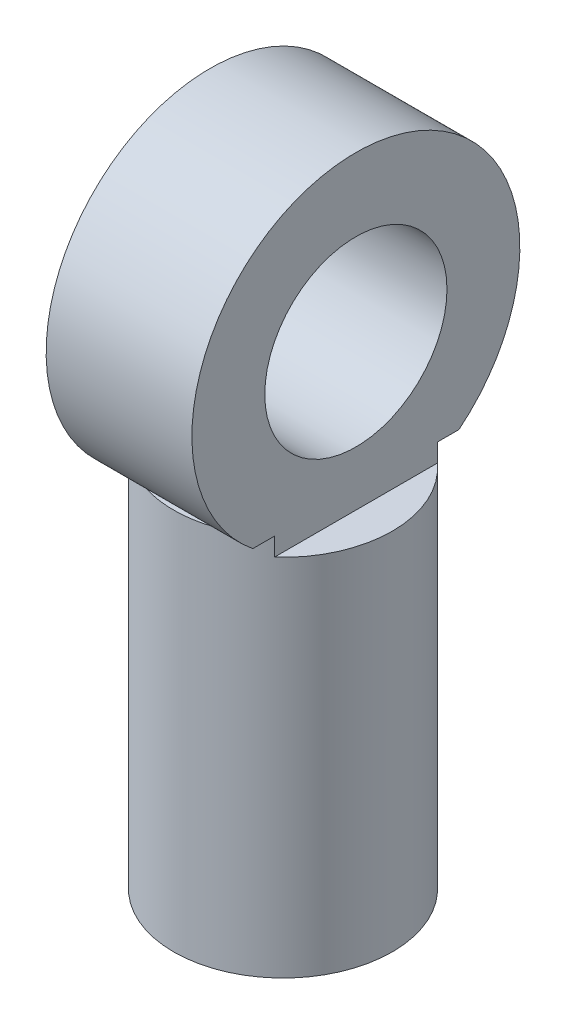
SolidWorks part; units mm, degrees
ref_plane "Front Plane" through (0, 0, 0) normal (0, 0, 1) x (1, 0, 0)
ref_plane "Top Plane" through (0, 0, 0) normal (0, 1, 0) x (1, 0, 0)
ref_plane "Right Plane" through (0, 0, 0) normal (1, 0, 0) x (0, 0, -1)
sketch "Sketch1" plane through (0, 0, 0) normal (0, 1, 0) x (1, 0, 0)
  circle A0 centre (0, 0) radius 3
  dimension "D1" = 6
extrude "crank_body" add sketch "Sketch1" along normal blind 10
sketch "Sketch2" plane through (0, 0, 0) normal (0, -1, 0) x (1, 0, 0)
  circle A0 centre (0, 0) radius 1.65
  dimension "D1" = 3.3
extrude "dowel_shaft" cut sketch "Sketch2" against normal blind 9
sketch "Sketch3" plane through (0, 0, 0) normal (1, 0, 0) x (0, 0, -1)
  line L0 (3, 10) -> (-3, 10) construction
  line L1 (-3, 10) -> (-3, 0) construction
  line L2 (-3, 10) -> (3, 10)
  line L3 (-3, 10) -> (-3, 10.5)
  line L4 (-3, 10.5) -> (3, 10.5)
  line L5 (3, 10) -> (3, 10.5)
  line L6 (3, 0) -> (3, 10) construction
  line L7 (-3, 10) -> (-3, 0) construction
  circle A0 centre (0, 14) radius 4.5
  dimension "D1" = 9
  dimension "D2" = 4
  dimension "D6" = 3
  dimension "D3" = 0.5
  dimension "D4" = 0
  dimension "D5" = 0
extrude "pin_shaft_body" add sketch "Sketch3" along normal blind 2 and the other way blind 2 contours A0 L3 L2 | L3 A0 L5 L4 | L5 A0 L3 L4 | L5 L4 L3 L2 region at (0, 10.1897, 2.6907) region at (0, 10.2628, 0) region at (0, 14.2525, 0)
sketch "Sketch4" plane through (2, 0, 0) normal (1, 0, 0) x (0, 0, -1)
  circle A0 centre (0, 14) radius 2.5
  dimension "D1" = 5
extrude "pin_shaft" cut sketch "Sketch4" against normal through all
extrude "smoothing_cuts" cut sketch "Sketch1<2>" along normal blind 10.5 flip side to cut
sketch "Sketch1<2>" plane through (0, 0, 0) normal (0, 1, 0) x (1, 0, 0) same geometry as "Sketch1"
